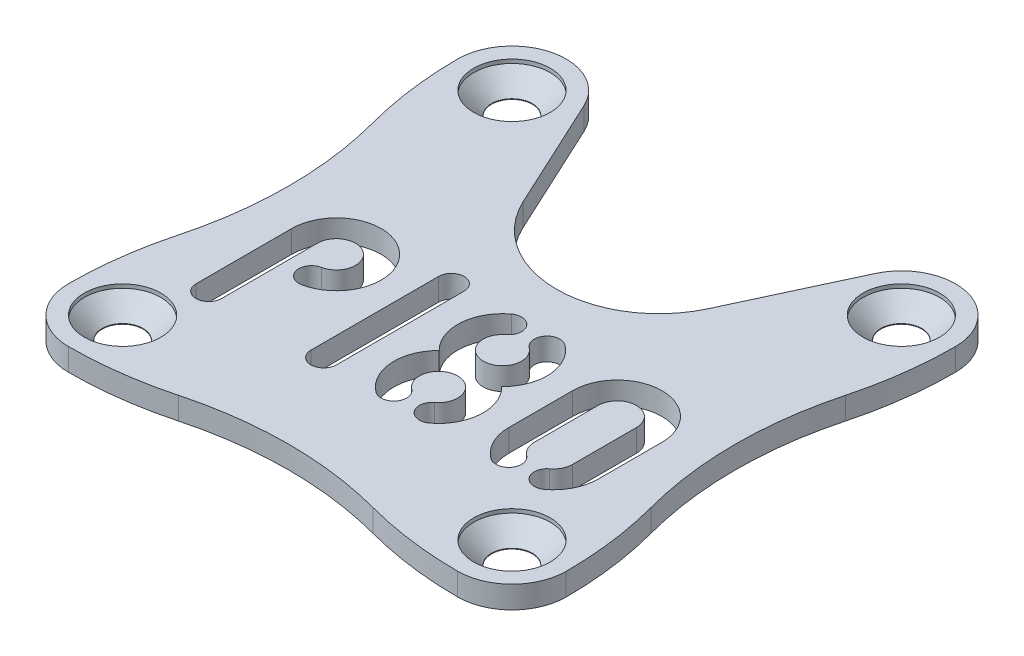
SolidWorks part; units mm, degrees
ref_plane "Front Plane" through (0, 0, 0) normal (0, 0, 1) x (1, 0, 0)
ref_plane "Top Plane" through (0, 0, 0) normal (0, 1, 0) x (1, 0, 0)
ref_plane "Right Plane" through (0, 0, 0) normal (1, 0, 0) x (0, 0, -1)
sketch "Sketch1" plane through (0, 0, 0) normal (0, 1, 0) x (1, 0, 0)
  line L0 (0, 19.5) -> (0, -19.5) construction
  line L1 (-19.5, 19.5) -> (19.5, 19.5)
  line L2 (-19.5, 19.5) -> (-19.5, -19.5)
  line L3 (-19.5, -19.5) -> (19.5, -19.5)
  line L4 (19.5, 19.5) -> (19.5, -19.5)
  line L5 (-19.5, 19.5) -> (19.5, -19.5) construction
  line L6 (-19.5, -19.5) -> (19.5, 19.5) construction
  line L7 (-19.5, 35.2) -> (-19.5, -19.5) construction
  circle A0 centre (-15.25, 15.25) radius 1.6
  circle A1 centre (15.25, 15.25) radius 1.6
  circle A2 centre (-15.25, -15.25) radius 1.6
  circle A3 centre (15.25, -15.25) radius 1.6
  circle A4 centre (15.25, 15.25) radius 1.6 construction
  circle A5 centre (15.25, -15.25) radius 1.6 construction
  circle A6 centre (-15.25, -15.25) radius 1.6 construction
  circle A7 centre (-15.25, 15.25) radius 1.6 construction
  point P0 (0, 0)
extrude "Shape" add sketch "Sketch1" along normal blind 1.75
sketch "Sketch2" plane through (0, 1.75, 0) normal (0, 1, 0) x (1, 0, 0)
  line L0 (0, 19.5) -> (0, -19.5) construction
  line L2 (-15.25, 16.85) -> (-15.25, -16.85) construction
  line L3 (-15.25, 0) -> (-19.5, 0) construction
  line L4 (-19.5, 19.5) -> (-19.5, -19.5) construction
  line L5 (19.5, 19.5) -> (-19.5, 19.5) construction
  line L6 (-19.5, -19.5) -> (19.5, -19.5) construction
  line L7 (-15.25, 0) -> (-11, 0) construction
  line L8 (-7.2551, 8.1291) -> (-12.5383, 19.5)
  line L9 (7.2551, 8.1291) -> (12.5383, 19.5)
  line L10 (-12.5383, 19.5) -> (12.5383, 19.5)
  line L14 (19.5, -19.5) -> (19.5, 19.5)
  line L15 (19.5, 19.5) -> (-19.5, 19.5)
  line L16 (-19.5, 19.5) -> (-19.5, -19.5)
  line L17 (-19.5, -19.5) -> (19.5, -19.5)
  line L18 (19.5, -19.5) -> (19.5, 19.5)
  line L19 (19.5, 19.5) -> (-19.5, 19.5)
  line L20 (-19.5, 19.5) -> (-19.5, -19.5)
  line L21 (-19.5, -19.5) -> (19.5, -19.5)
  circle A0 centre (0, 11.5) radius 8
  circle A1 centre (-15.25, 15.25) radius 1.6 construction
  circle A2 centre (-15.25, -15.25) radius 1.6 construction
  circle A3 centre (-15.25, 15.25) radius 4.25
  circle A4 centre (15.25, 15.25) radius 4.25
  circle A5 centre (-15.25, -15.25) radius 4.25
  circle A6 centre (15.25, -15.25) radius 4.25
  line M3 (19.5, -19.5) -> (19.5, 19.5)
  line M4 (19.5, 19.5) -> (-19.5, 19.5)
  line M5 (-19.5, 19.5) -> (-19.5, -19.5)
  line M6 (-19.5, -19.5) -> (19.5, -19.5)
  dimension "D1" = 16
  dimension "D2" = 0
extrude "Camera cut" cut sketch "Sketch2" against normal up to next contours A0 L10 L8 | A0 | A0 L9 M4 | A3 L8 M4 | A4 L9 M4 | A3 L19 M5 | A4 L18 M4 | A6 M6 M3 | A5 M5 M6
sketch "Sketch4" plane through (0, 1.75, 0) normal (0, 1, 0) x (1, 0, 0)
  circle A0 centre (-15.25, 15.25) radius 3
  circle A1 centre (15.25, 15.25) radius 3
  circle A2 centre (15.25, -15.25) radius 3
  circle A3 centre (-15.25, -15.25) radius 3
  dimension "D1" = 6
extrude "Screw head cuts" cut sketch "Sketch4" against normal blind 0.3
chamfer "Screw head chamfers" distance 1.4 angle 45 4 edges at (-15.25, 1.45, 16.85) (15.25, 1.45, 16.85) (15.25, 1.45, -13.65) (-15.25, 1.45, -13.65)
sketch "Sketch5" plane through (0, 1.75, 0) normal (0, 1, 0) x (1, 0, 0)
  line L0 (-19.5, 15.25) -> (19.5, 15.25) construction
  line L1 (-19.5, -15.25) -> (19.5, -15.25) construction
  line L2 (0, -19.5) -> (0, 15.25) construction
  line L3 (-15.25, -19.5) -> (15.25, -19.5) construction
  line L4 (-17.5, 18.8556) -> (-17.5, -18.8556) construction
  line L5 (-19.5, 15.25) -> (-19.5, -15.25) construction
  line L6 (-17.5, 0) -> (0, 0) construction
  line L7 (-18.5, 17.9886) -> (-18.5, -17.9886) construction
  line L8 (-18.5, 0) -> (-17.5, 0) construction
  line L9 (-18.5, 0) -> (-19.5, 0) construction
  line L10 (-17.5, 0) -> (-19.5, 15.25) construction
  line L11 (-15.25, 15.25) -> (15.25, -15.25) construction
  line L12 (-18.5, 7.625) -> (-17.5, 7.625) construction
  line L13 (-19.5, 15.25) -> (-19.5, -15.25)
  line L14 (-15.25, -19.5) -> (15.25, -19.5)
  line L15 (19.5, -15.25) -> (19.5, 15.25)
  arc A0 (-19.5, -15.25) -> (-15.25, -19.5) centre (-15.25, -15.25) ccw construction
  arc A1 (-11.3957, 17.0408) -> (-19.5, 15.25) centre (-15.25, 15.25) ccw construction
  arc A2 (-19.5, 15.25) -> (-18.5, 7.625) centre (10.0703, 15.25) ccw
  arc A3 (-18.5, 7.625) -> (-18.5, -7.625) centre (-47.0703, 0) cw
  arc A4 (-19.5, -15.25) -> (-18.5, -7.625) centre (10.0703, -15.25) cw
  arc A5 (19.5, -15.25) -> (18.5, -7.625) centre (-10.0703, -15.25) ccw
  arc A6 (18.5, 7.625) -> (18.5, -7.625) centre (47.0703, 0) ccw
  arc A7 (19.5, 15.25) -> (18.5, 7.625) centre (-10.0703, 15.25) cw
  arc A8 (15.25, -19.5) -> (7.625, -18.5) centre (15.25, 10.0703) cw
  arc A9 (-7.625, -18.5) -> (7.625, -18.5) centre (0, -47.0703) cw
  arc A10 (-15.25, -19.5) -> (-7.625, -18.5) centre (-15.25, 10.0703) ccw
  dimension "D1" = 2
extrude "Beauty cuts" cut sketch "Sketch5" against normal up to next
sketch "Sketch9" plane through (0, 1.75, 0) normal (0, 1, 0) x (1, 0, 0)
  line L0 (-19.0742, -10.25) -> (19.0742, -10.25) construction
  line L1 (-13.5, -2.4579) -> (-13.5, -12.0246) construction
  line L2 (-17.5011, -0.25) -> (17.5011, -0.25) construction
  line L3 (-13.5, -10.25) -> (-13.5, -0.25) construction
  line L4 (-14.5, -10.25) -> (-14.5, -0.25)
  line L5 (-12.5, -10.25) -> (-12.5, -0.25)
  line L6 (-17.6282, -2.75) -> (17.6282, -2.75) construction
  line L7 (-13.5, 0.75) -> (-11, 0.75)
  line L8 (-14.5, -5.25) -> (-12.5, -5.25) construction
  line L9 (-11, -4.25) -> (-11, -6.25) construction
  line L10 (-4.5, 8.8583) -> (-4.5, -11.9643) construction
  line L11 (17.5011, -0.25) -> (17.5011, -10.25) construction
  line L12 (-17.9698, -5.25) -> (17.9698, -5.25) construction
  line L13 (-15.25, -15.25) -> (15.25, -15.25) construction
  line L14 (-4.5, -0.25) -> (-4.5, -10.25) construction
  line L15 (-3.5, -0.25) -> (-3.5, -10.25)
  line L16 (-5.5, -0.25) -> (-5.5, -10.25)
  line L17 (-5.5, -10.25) -> (-3.5, -10.25) construction
  line L18 (2, -2.4583) -> (2, -12.0116) construction
  line L19 (-17.5095, 0.75) -> (17.5095, 0.75) construction
  line L20 (-17.5264, -1.25) -> (17.5264, -1.25) construction
  line L21 (18.5331, -7.75) -> (-18.5331, -7.75) construction
  line L22 (0, 0.75) -> (0, -15.25) construction
  line L23 (11, 16.2381) -> (11, -30.4508) construction
  line L24 (7.5, -7.75) -> (7.5, -2.75)
  line L25 (14.5, -2.75) -> (14.5, -7.75)
  line L26 (-7.5, 0.75) -> (-7.5, -15.25) construction
  line L27 (-1.5, 0.75) -> (-1.5, -15.25) construction
  line L28 (5.5, 0.75) -> (5.5, -15.25) construction
  line L29 (-7.5, -7.25) -> (-5.5, -7.25) construction
  line L30 (-3.5, -5.25) -> (-1.5, -5.25) construction
  line L31 (5.5, -7.25) -> (7.5, -7.25) construction
  line L32 (-14.5, -10.25) -> (-14.5, -15.25) construction
  line L33 (14.5, -7.75) -> (14.5, -15.25) construction
  line L34 (-14.5, -12.75) -> (14.5, -12.75) construction
  line L35 (9.5, -2.75) -> (9.5, -7.75)
  line L36 (12.5, -2.75) -> (12.5, -7.75)
  line L37 (9.5, -7.75) -> (9.5, -10.9123) construction
  line L38 (0.5, -2.75) -> (0.5, 0.4123) construction
  line L39 (-11.5, -5.1995) -> (-12.5, -5.1995) construction
  arc A0 (-18.5, -7.625) -> (-18.5, 7.625) centre (-47.0703, 0) ccw construction
  arc A1 (18.5, 7.625) -> (18.5, -7.625) centre (47.0703, 0) ccw construction
  arc A2 (-14.5, -10.25) -> (-12.5, -10.25) centre (-13.5, -10.25) ccw
  arc A3 (-12.5, -0.25) -> (-14.5, -0.25) centre (-13.5, -0.25) ccw
  circle A4 centre (-11, -2.75) radius 3.5
  circle A5 centre (-11, -2.75) radius 1.5
  circle A6 centre (-10.5, -5.1995) radius 1
  arc A7 (-18.5, -7.625) -> (-19.5, -15.25) centre (10.0703, -15.25) ccw construction
  arc A8 (19.5, -15.25) -> (18.5, -7.625) centre (-10.0703, -15.25) ccw construction
  arc A9 (-3.5, -0.25) -> (-5.5, -0.25) centre (-4.5, -0.25) ccw
  arc A10 (-5.5, -10.25) -> (-3.5, -10.25) centre (-4.5, -10.25) ccw
  circle A11 centre (2, -2.75) radius 3.5
  circle A12 centre (2, -2.75) radius 1.5
  circle A13 centre (2, -7.75) radius 3.5
  circle A14 centre (2, -7.75) radius 1.5
  circle A15 centre (0.5, -0.75) radius 1
  circle A16 centre (3.5, -0.75) radius 1
  circle A17 centre (9.5, -9.75) radius 1
  circle A18 centre (12.5, -9.75) radius 1
  circle A19 centre (11, -2.75) radius 3.5
  circle A20 centre (11, -2.75) radius 1.5
  circle A21 centre (11, -7.75) radius 3.5
  circle A22 centre (11, -7.75) radius 1.5
  circle A23 centre (0.5, -9.75) radius 1
  circle A24 centre (3.5, -9.75) radius 1
  point P16 (-13.5, -5.25)
  point P23 (-13.5, -0.25)
  point P41 (17.5011, -5.25)
  point P47 (-4.5, -5.25)
  point P106 (0, -12.75)
  dimension "D1" = 1
  dimension "D2" = 10
  dimension "D3" = 2
  dimension "D4" = 2.5
  dimension "D5" = 5
extrude "Name" cut sketch "Sketch9" against normal up to next
sketch "Eight milling sketch" plane through (0, 0, 0) normal (0, -1, 0) x (1, 0, 0)
  line L0 (0.5, 7.75) -> (-0.5, 7.75) construction
  line L1 (-0.5, 7.75) -> (-1.5, 7.75) construction
  line L2 (1.5, 9.75) -> (2.5, 9.75) construction
  line L3 (1.5, 0.75) -> (2.5, 0.75) construction
  arc A0 (0.5, 9.75) -> (3.5, 9.75) centre (2, 7.75) ccw
  arc A1 (1.4038, 0.3221) -> (2.5962, 0.3221) centre (2, 2.75) ccw
  arc A2 (1.1, 8.95) -> (2.9, 8.95) centre (2, 7.75) ccw construction
  arc A3 (-0.1, 10.55) -> (-0.4495, 5.25) centre (2, 7.75) ccw construction
  arc A4 (1.5, 9.75) -> (1.4038, 10.1779) centre (0.5, 9.75) ccw
  arc A5 (1.1, 8.95) -> (-0.1, 10.55) centre (0.5, 9.75) ccw construction
  arc A6 (2.5962, 10.1779) -> (2.5, 9.75) centre (3.5, 9.75) ccw
  arc A7 (4.1, 10.55) -> (2.9, 8.95) centre (3.5, 9.75) ccw construction
  arc A8 (2.5962, 10.1779) -> (1.4038, 10.1779) centre (2, 7.75) ccw
  arc A9 (1.4038, 0.3221) -> (1.5, 0.75) centre (0.5, 0.75) ccw
  arc A10 (-0.1, -0.05) -> (1.1, 1.55) centre (0.5, 0.75) ccw construction
  arc A11 (2.5, 0.75) -> (2.5962, 0.3221) centre (3.5, 0.75) ccw
  arc A12 (2.9, 1.55) -> (4.1, -0.05) centre (3.5, 0.75) ccw construction
  arc A13 (3.5, 0.75) -> (0.5, 0.75) centre (2, 2.75) ccw
ref_point "Milling home point"
